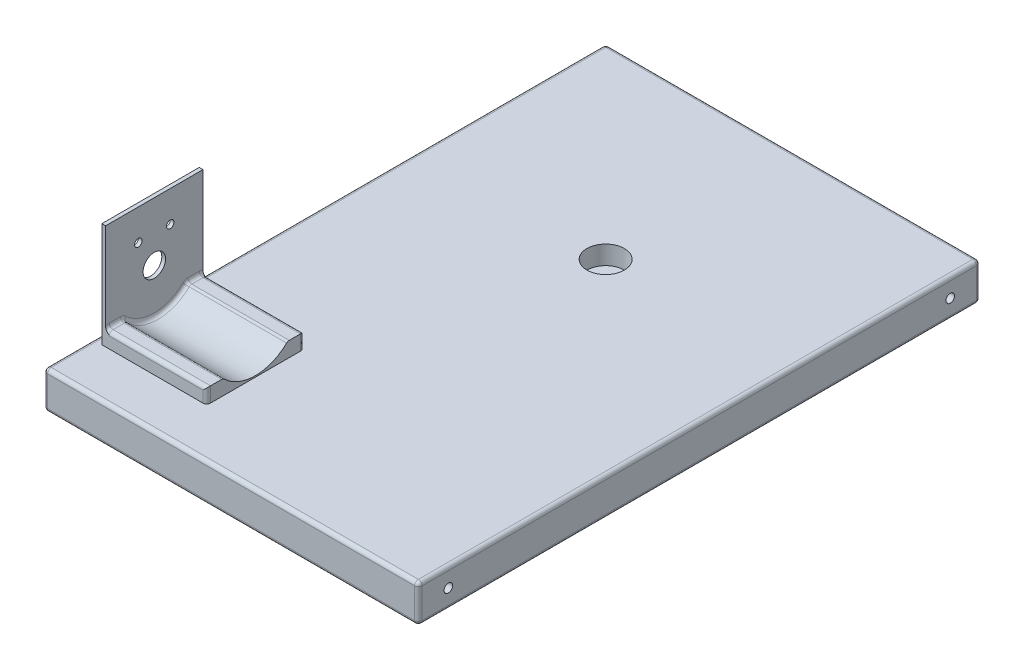
SolidWorks part; units mm, degrees
material "ABS"
ref_plane "Front Plane" through (0, 0, 0) normal (0, 0, 1) x (1, 0, 0)
ref_plane "Top Plane" through (0, 0, 0) normal (0, 1, 0) x (1, 0, 0)
ref_plane "Right Plane" through (0, 0, 0) normal (1, 0, 0) x (0, 0, -1)
sketch "Sketch2" plane through (0, 0, 0) normal (0, 1, 0) x (1, 0, 0)
  line L0 (0, 0) -> (0, 150)
  line L1 (0, 150) -> (100, 150)
  line L2 (100, 150) -> (100, 0)
  line L3 (100, 0) -> (0, 0)
  dimension "D1" = 100
  dimension "D2" = 150
extrude "Boss-Extrude1" add sketch "Sketch2" along normal blind 10
sketch "Sketch3" plane through (0, 10, 0) normal (0, 1, 0) x (1, 0, 0)
  line L0 (50, 150) -> (50, 100) construction
  line L1 (100, 150) -> (0, 150) construction
  circle A0 centre (50, 100) radius 5
  dimension "D2" = 10
  dimension "D1" = 50
extrude "MountHole" cut sketch "Sketch3" against normal blind 5
sketch "Sketch4" plane through (0, 0, 0) normal (-1, 0, 0) x (0, 0, 1)
  line L0 (-8, 10) -> (-8, 0) construction
  line L1 (-150, 10) -> (0, 10) construction
  line L2 (-150, 0) -> (0, 0) construction
  line L3 (0, 10) -> (0, 0) construction
  circle A0 centre (-8, 5) radius 1.15
  dimension "D2" = 2.3
  dimension "D1" = 8
extrude "Cut-Extrude2" cut sketch "Sketch4" against normal through all
sketch "Sketch5" plane through (0, 0, 0) normal (-1, 0, 0) x (0, 0, 1)
  line L0 (-142, 10) -> (-142, 0) construction
  line L1 (-150, 10) -> (0, 10) construction
  line L2 (-150, 0) -> (0, 0) construction
  line L3 (-150, 10) -> (-150, 0) construction
  circle A0 centre (-142, 5) radius 1.15
  dimension "D2" = 2.3
  dimension "D1" = 8
extrude "Cut-Extrude3" cut sketch "Sketch5" against normal through all
fillet "Fillet1" [suppressed] radius 2
sketch "Sketch7" plane through (0, 10, 0) normal (0, 1, 0) x (1, 0, 0)
  line L0 (11, 0) -> (11, 26) construction
  line L1 (0, 0) -> (100, 0) construction
  line L2 (0, 150) -> (0, 0) construction
  line L3 (11, 26) -> (47.1706, 26) construction
  line L9 (11, 26) -> (-5.1328, 26) construction
  line L15 (2.5, 39) -> (2.5, 13)
  line L16 (2.5, 39) -> (30.5, 39)
  line L17 (30.5, 39) -> (30.5, 13)
  line L18 (30.5, 13) -> (2.5, 13)
  point P10 (2.5, 26)
  dimension "D1" = 26
  dimension "D2" = 11
  dimension "D3" = 26
  dimension "D4" = 28
  dimension "D5" = 8.5
extrude "Boss-Extrude2" add sketch "Sketch7" along normal blind 4
sketch "Sketch10" plane through (0, 14, 0) normal (0, 1, 0) x (1, 0, 0)
  line L0 (2.5, 39) -> (2.5, 13)
  line L1 (2.5, 13) -> (3.5, 13)
  line L2 (2.5, 13) -> (30.5, 13) construction
  line L3 (3.5, 13) -> (3.5, 39)
  line L4 (30.5, 39) -> (2.5, 39) construction
  line L5 (3.5, 39) -> (2.5, 39)
  dimension "D1" = 1
extrude "Boss-Extrude3" add sketch "Sketch10" along normal blind 24
sketch "Sketch11" plane through (30.5, 0, 0) normal (1, 0, 0) x (0, 0, -1)
  line L0 (13, 14) -> (39, 14) construction
  line L1 (13, 14) -> (17.3857, 14)
  line L2 (34.6143, 14) -> (39, 14)
  arc A0 (17.3857, 14) -> (34.6143, 14) centre (26, 22.3543) ccw
  dimension "D1" = 12
extrude "Cut-Extrude5" cut sketch "Sketch11" against normal blind 27 and the other way through all
sketch "Sketch13" plane through (2.5, 0, 0) normal (-1, 0, 0) x (0, 0, 1)
  line L0 (-26, 10) -> (-26, 22.354) construction
  line L1 (-39, 10) -> (-13, 10) construction
  line L2 (-26, 22.354) -> (-21.75, 29.7152) construction
  line L3 (-26, 22.354) -> (-6.4369, 22.354) construction
  line L4 (-26, 22.354) -> (-30.25, 29.7152) construction
  circle A0 centre (-26, 22.354) radius 3
  circle A1 centre (-21.75, 29.7152) radius 1
  circle A2 centre (-30.25, 29.7152) radius 1
  dimension "D2" = 6
  dimension "D5" = 2
  dimension "D8" = 2
  dimension "D1" = 12.354
  dimension "D3" = 60
  dimension "D4" = 8.5
  dimension "D6" = 120
  dimension "D7" = 8.5
extrude "Cut-Extrude6" cut sketch "Sketch13" against normal up to surface (1 mm away) up to face at (3.5, 21.3924, -26)
fillet "Fillet2" radius 1 6 edges at (30.5, 12, -39) (17, 14, -39) (17, 14, -34.6143) (17, 14, -17.3857) (30.5, 12, -13) (17, 14, -13)
fillet "Fillet3" radius 1 7 edges at (3.5, 13.7071, -38.7071) (3.5, 14, -36.5138) (3.5, 13.9272, -34.6531) (3.5, 13.7071, -13.2929) (3.5, 14, -15.4862) (3.5, 13.9272, -17.3469) (3.5, 10.3543, -26)
fillet "Fillet4" radius 1 12 edges at (50, 0, -150) (100, 5, -150) (50, 10, -150) (0, 5, -150) (0, 0, -75) (0, 10, -75) (100, 0, -75) (100, 10, -75) (100, 5, 0) (50, 0, 0) (50, 10, 0) (0, 5, 0)
